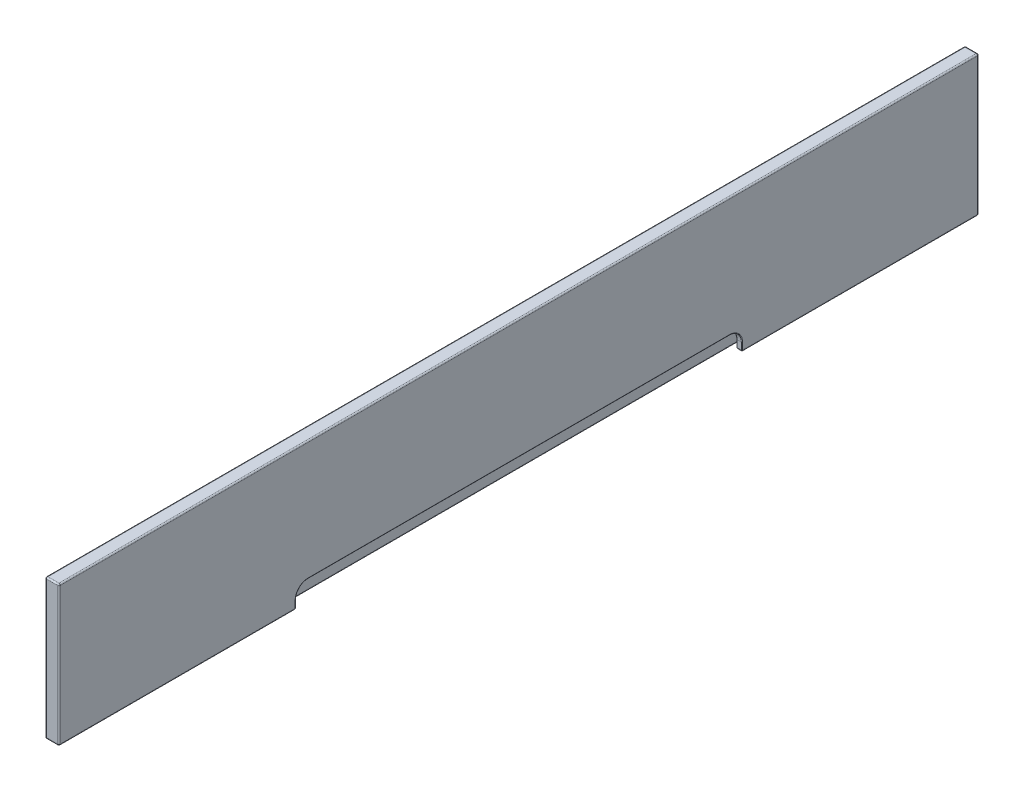
SolidWorks part; units mm, degrees
ref_plane "Front Plane" through (0, 0, 0) normal (0, 0, 1) x (1, 0, 0)
ref_plane "Top Plane" through (0, 0, 0) normal (0, 1, 0) x (1, 0, 0)
ref_plane "Right Plane" through (0, 0, 0) normal (1, 0, 0) x (0, 0, -1)
sketch "Sketch1" plane through (0, 0, 0) normal (1, 0, 0) x (0, 0, -1)
  line L1 (670, -102) -> (-670, -102)
  line L2 (670, -102) -> (670, 102)
  line L3 (670, 102) -> (-670, 102)
  line L4 (-670, -102) -> (-670, 102)
  line L5 (670, -102) -> (-670, 102) construction
  line L6 (670, 102) -> (-670, -102) construction
  point P0 (0, 0)
  dimension "D1" = 1340
  dimension "D2" = 204
extrude "Boss-Extrude1" add sketch "Sketch1" against normal blind 20
sketch "Sketch3" plane through (0, 0, 0) normal (1, 0, 0) x (0, 0, -1)
  line L0 (-670, -102) -> (670, -102) construction
  line L1 (-325, -102) -> (325, -102)
  line L2 (-325, -102) -> (-325, -90)
  line L3 (-307, -72) -> (307, -72)
  line L4 (325, -102) -> (325, -90)
  arc A0 (307, -72) -> (325, -90) centre (307, -90) cw
  arc A1 (-325, -90) -> (-307, -72) centre (-307, -90) cw
  point P4 (0, -102)
  point P10 (325, -72)
  point P13 (-325, -72)
  dimension "D3" = 18
  dimension "D1" = 30
  dimension "D2" = 650
extrude "Cut-Extrude2" cut sketch "Sketch3" against normal blind 15
sketch "Sketch4" plane through (-15, 0, 0) normal (1, 0, 0) x (0, 0, -1)
  line L0 (-325, -102) -> (325, -102) construction
  line L1 (-335, -102) -> (335, -102)
  line L2 (-335, -102) -> (-335, -85)
  line L3 (-312, -62) -> (312, -62)
  line L4 (335, -102) -> (335, -85)
  arc A0 (312, -62) -> (335, -85) centre (312, -85) cw
  arc A1 (-335, -85) -> (-312, -62) centre (-312, -85) cw
  point P6 (0, -62)
  point P10 (335, -62)
  point P13 (-335, -62)
  dimension "D3" = 23
  dimension "D1" = 670
  dimension "D2" = 40
extrude "Cut-Extrude3" cut sketch "Sketch4" along normal blind 7
fillet "Fillet1" radius 1 20 edges at (-8, -93.5, -335) (-8, -68.7365, -328.2635) (-8, -62, 0) (-8, -93.5, 335) (0, -96, -325) (0, -77.2721, -319.7279) (0, -96, 325) (0, -77.2721, 319.7279) (-8, -96, -325) (-8, -77.2721, -319.7279) (-8, -96, 325) (-8, -77.2721, 319.7279) (-15, -93.5, -335) (-15, -68.7365, -328.2635) (-15, -93.5, 335) (-15, -68.7365, 328.2635) (-8, -68.7365, 328.2635) (0, -72, 0) (-8, -72, 0) (-15, -62, 0)
fillet "Fillet2" radius 2 28 edges at (-10, -102, -670) (-0.2929, -102, 325.2929) (-4, -102, 325) (-7.7071, -102, 325.2929) (-8, -102, 330) (-8.2929, -102, 334.7071) (-11.5, -102, 335) (-14.7071, -102, 334.7071) (-15, -102, 0) (-14.7071, -102, -334.7071) (-11.5, -102, -335) (-8.2929, -102, -334.7071) (-8, -102, -330) (-7.7071, -102, -325.2929) (-4, -102, -325) (-0.2929, -102, -325.2929) (-10, -102, 670) (-20, -102, 0) (-20, 0, -670) (-20, 0, 670) (-10, 102, 670) (-20, 102, 0) (-10, 102, -670) (0, -102, 498) (0, 0, 670) (0, 102, 0) (0, 0, -670) (0, -102, -498)
